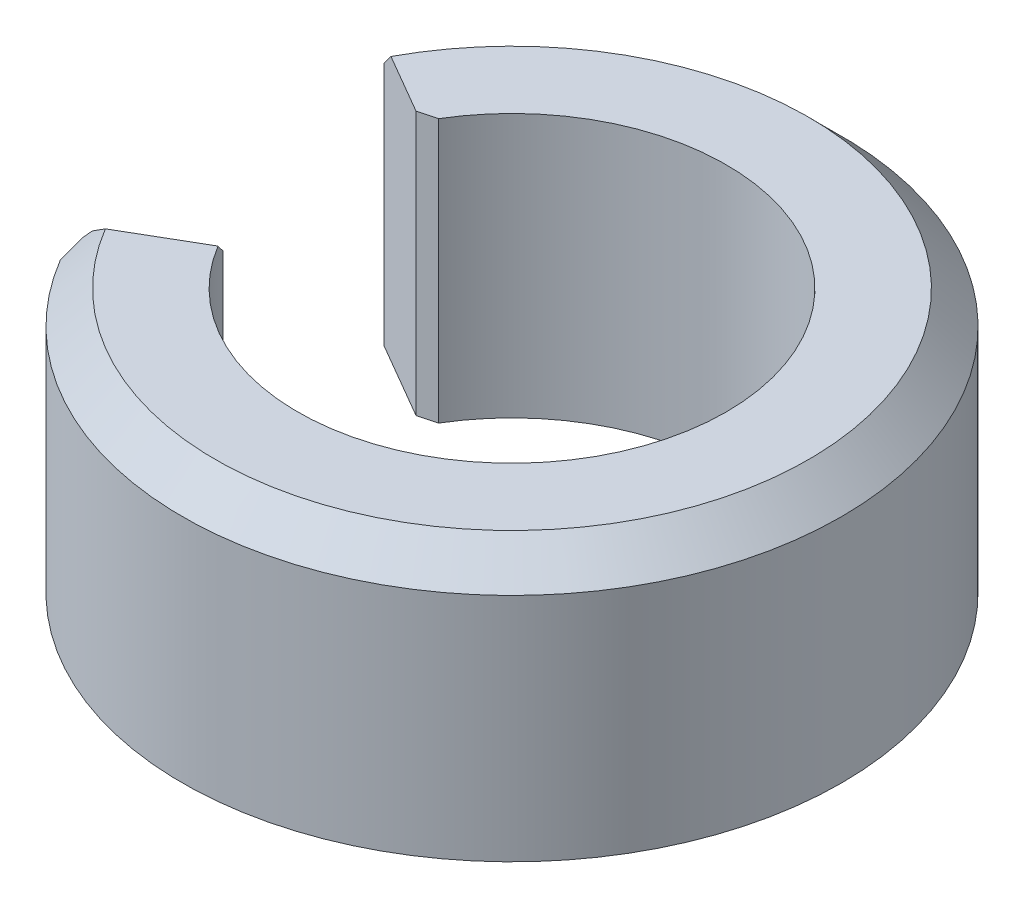
SolidWorks part; units mm, degrees
ref_plane "Front Plane" through (0, 0, 0) normal (0, 0, 1) x (1, 0, 0)
ref_plane "Top Plane" through (0, 0, 0) normal (0, 1, 0) x (1, 0, 0)
ref_plane "Right Plane" through (0, 0, 0) normal (1, 0, 0) x (0, 0, -1)
sketch "Sketch1" plane through (0, 0, 0) normal (0, 1, 0) x (1, 0, 0)
  line L0 (-4.3974, 2.3797) -> (-2.8831, 1.5)
  line L1 (-4.3974, -2.3797) -> (-2.8831, -1.5)
  line L2 (0, 0) -> (-11.0056, 0) construction
  circle A0 centre (0, 0) radius 5
  circle A1 centre (0, 0) radius 3.25
  dimension "D1" = 6.5
  dimension "D2" = 10
  dimension "D3" = 3
  dimension "D4" = 60.312
extrude "Boss-Extrude1" add sketch "Sketch1" along normal blind 4 contours A1 L1 A0 L0 region at (1.1937, 0, -4.714)
chamfer "Chamfer1" distance 0.2 angle 45 4 edges at (-3.6403, 4, 1.9399) (-4.3974, 2, 2.3797) (-4.3974, 2, -2.3797) (-2.8831, 2, -1.5) first distance on face at (-3.6403, 2, 1.9399) first distance on face at (0.3013, 2, 0) first distance on face at (-3.6403, 2, -1.9399)
chamfer "Chamfer2" distance 0.5 angle 45 1 edges at (5, 4, -0.0029)
